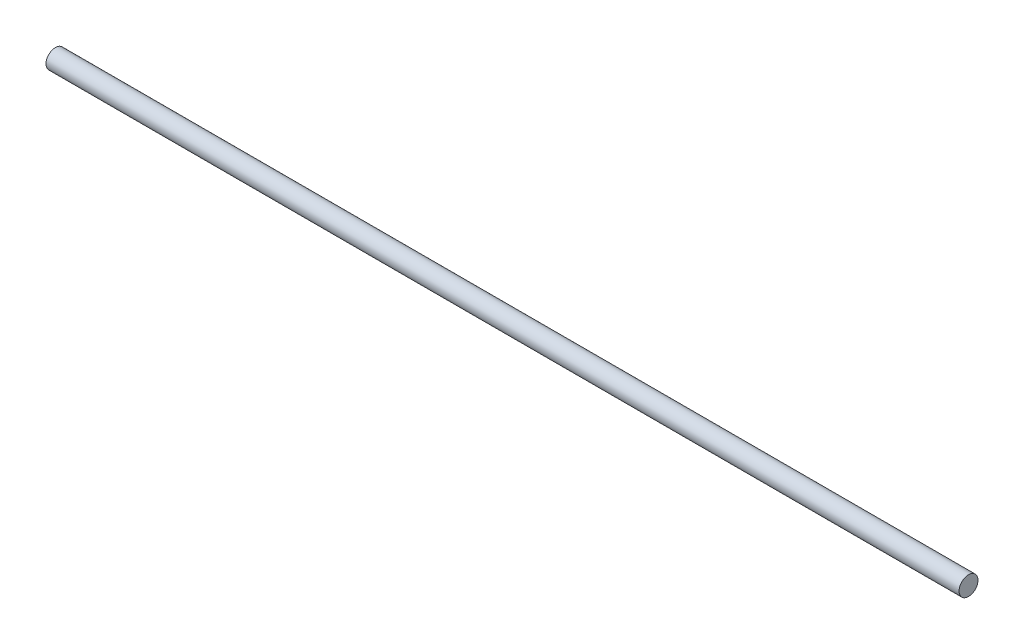
SolidWorks part; units mm, degrees
material "6061-T4 (SS)"
ref_plane "Front Plane" through (0, 0, 0) normal (0, 0, 1) x (1, 0, 0)
ref_plane "Top Plane" through (0, 0, 0) normal (0, 1, 0) x (1, 0, 0)
ref_plane "Right Plane" through (0, 0, 0) normal (1, 0, 0) x (0, 0, -1)
sketch "Sketch1" plane through (0, 0, 0) normal (1, 0, 0) x (0, 0, -1)
  circle A0 centre (0, 0) radius 12.5
  dimension "D1" = 25
extrude "Boss-Extrude1" add sketch "Sketch1" along normal blind 603.5 and the other way blind 603.5
sketch "Sketch2" plane through (0, 0, 0) normal (0, 0, 1) x (1, 0, 0)
  line L0 (0, 0) -> (-603.5, 0)
  line L1 (-603.5, 12.5) -> (-603.5, -12.5) construction
  circle A0 centre (-603.5, 0) radius 20
  circle A1 centre (-603.5, 0) radius 270
  point P7 (-583.5, 0)
  point P8 (-333.5, 0)
  point P9 (-583.5, 0)
  dimension "D1" = 40
  dimension "D2" = 540
ref_plane "Plane1" through (301.75, 0, 0) normal (1, 0, 0) x (0, 0, -1)
ref_plane "Plane2" through (-311, 0, 0) normal (1, 0, 0) x (0, 0, -1)
